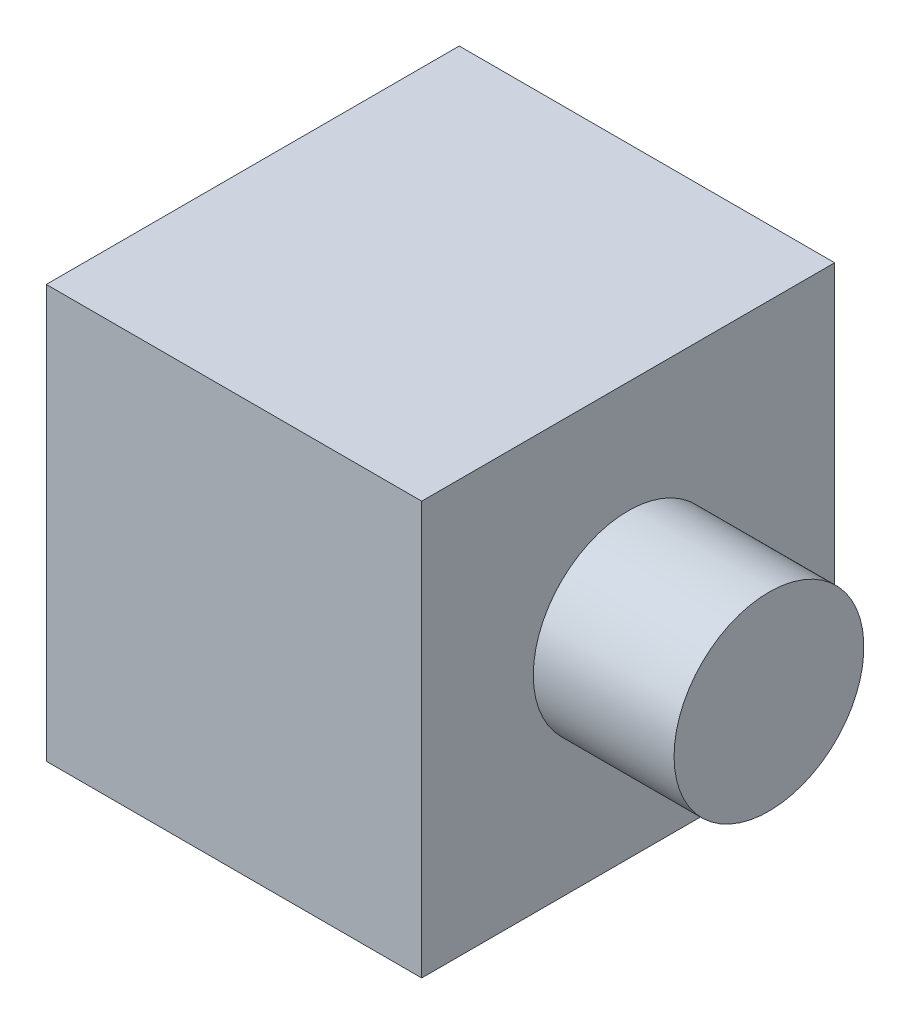
SolidWorks part; units mm, degrees
ref_plane "Front Plane" through (0, 0, 0) normal (0, 0, 1) x (1, 0, 0)
ref_plane "Top Plane" through (0, 0, 0) normal (0, 1, 0) x (1, 0, 0)
ref_plane "Right Plane" through (0, 0, 0) normal (1, 0, 0) x (0, 0, -1)
sketch "Block Sketch" plane through (0, 0, 0) normal (0, 0, 1) x (1, 0, 0)
  line L0 (-40, -22) -> (0, -22)
  line L1 (0, -22) -> (0, 22)
  line L2 (0, 22) -> (-40, 22)
  line L3 (-40, 22) -> (-40, -22)
extrude "Block" add sketch "Block Sketch" along normal mid plane 44
ref_axis "Engine Axis" through (17.75, 0, 0) along (-1, 0, 0)
sketch "Neck Sketch" plane through (0, 0, 0) normal (0, 0, 1) x (1, 0, 0)
  line L0 (-1000, 0) -> (1000, 0) construction
  line L1 (0, 0) -> (15, 0)
  line L2 (15, 0) -> (15, 10.1125)
  line L3 (15, 10.1125) -> (0, 10.1125)
  line L4 (0, 10.1125) -> (0, 0)
revolve "Neck" add sketch "Neck Sketch" angle 360 about L0
sketch "Regulator Port Sketch" plane through (0, 0, 0) normal (0, 0, 1) x (1, 0, 0)
  line L0 (-1000, 0) -> (1000, 0) construction
  line L1 (-41, 0) -> (-26, 0)
  line L2 (-26, 0) -> (-26, 7.2)
  line L3 (-26, 7.2) -> (-41, 7.2)
  line L4 (-41, 7.2) -> (-41, 0)
revolve "Regulator Port" cut sketch "Regulator Port Sketch" angle 360 about L0
sketch "Side Port -Y Sketch" plane through (0, 0, 0) normal (0, 0, 1) x (1, 0, 0)
  line L0 (-20, -40) -> (-20, 40) construction
  line L1 (-20, -23) -> (-14.5, -23)
  line L2 (-14.5, -23) -> (-14.5, -8)
  line L3 (-14.5, -8) -> (-20, -8)
  line L4 (-20, -8) -> (-20, -23)
revolve "Side Port -Y" cut sketch "Side Port -Y Sketch" angle 360 about L0
